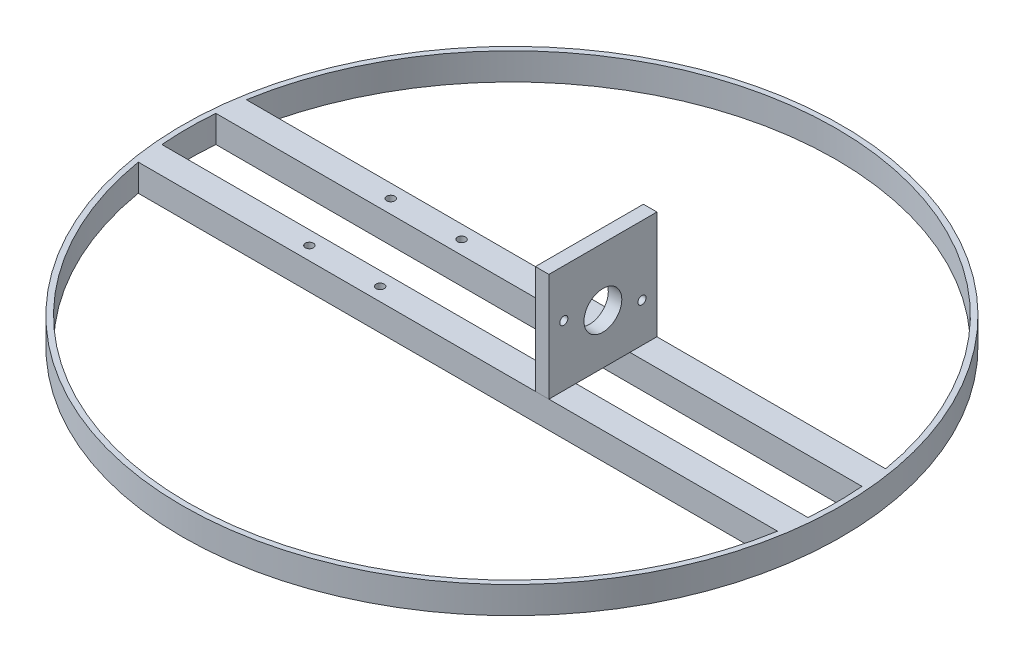
SolidWorks part; units mm, degrees
ref_plane "Front Plane" through (0, 0, 0) normal (0, 0, 1) x (1, 0, 0)
ref_plane "Top Plane" through (0, 0, 0) normal (0, 1, 0) x (1, 0, 0)
ref_plane "Right Plane" through (0, 0, 0) normal (1, 0, 0) x (0, 0, -1)
sketch "Sketch1" plane through (0, 0, 0) normal (0, 1, 0) x (1, 0, 0)
  circle A0 centre (-133.6717, -100.8607) radius 122
  circle A1 centre (-133.6717, -100.8607) radius 120
  dimension "D1" = 244
  dimension "D2" = 2
extrude "Boss-Extrude1" add sketch "Sketch1" along normal blind 10
sketch "Sketch2" plane through (0, 0, 0) normal (1, 0, 0) x (0, 0, -1)
  line L0 (-100.8607, 10) -> (-100.8607, -30.5393) construction
  line L1 (21.1393, 10) -> (-222.8607, 10) construction
  line L2 (-222.8607, 0) -> (21.1393, 0) construction
  line L3 (-120.8607, 10) -> (-110.8607, 10)
  line L4 (-120.8607, 10) -> (-120.8607, 0)
  line L5 (-120.8607, 0) -> (-110.8607, 0)
  line L6 (-110.8607, 10) -> (-110.8607, 0)
  line L8 (-90.8607, 10) -> (-90.8607, 0)
  line L9 (-80.8607, 0) -> (-90.8607, 0)
  line L10 (-80.8607, 10) -> (-80.8607, 0)
  line L11 (-80.8607, 10) -> (-90.8607, 10)
  dimension "D1" = 10
extrude "Boss-Extrude2" add sketch "Sketch2" against normal blind 300
sketch "Sketch3" plane through (0, 0, 0) normal (0, 1, 0) x (1, 0, 0)
  line L0 (-133.6717, -90.8607) -> (-133.6717, -110.8607) construction
  line L1 (-253.2543, -90.8607) -> (-14.0891, -90.8607) construction
  line L2 (-253.2543, -110.8607) -> (-14.0891, -110.8607) construction
  circle A0 centre (-133.6717, -100.8607) radius 122
extrude "Cut-Extrude5" cut sketch "Sketch3" against normal through all and the other way through all flip side to cut contours A0
sketch "Sketch4" plane through (0, 0, 0) normal (1, 0, 0) x (0, 0, -1)
  line L0 (21.1393, 10) -> (-222.8607, 10) construction
  line L1 (-120.8607, 10) -> (-80.8607, 10)
  line L2 (-120.8607, 10) -> (-120.8607, 50)
  line L3 (-120.8607, 50) -> (-80.8607, 50)
  line L4 (-80.8607, 50) -> (-80.8607, 10)
  line L5 (-120.8607, 10) -> (-220.8607, 10) construction
  line L7 (-100.8607, 50) -> (-100.8607, 10) construction
  line L8 (-100.8607, 30) -> (-80.8607, 30) construction
  circle A0 centre (-86.3892, 24.5198) radius 1.5
  circle A1 centre (-115.3323, 32.4125) radius 1.5
  circle A2 centre (-100.8607, 28.4662) radius 7
  dimension "D3" = 14
  dimension "D1" = 40
  dimension "D2" = 40
extrude "Boss-Extrude3" add sketch "Sketch4" along normal blind 5 from offset 105 separate body offset against normal yes
sketch "Sketch6" plane through (0, 0, 0) normal (0, 1, 0) x (1, 0, 0)
  line L0 (-133.6717, -80.8607) -> (-133.6717, -120.8607) construction
  line L1 (-251.9933, -80.8607) -> (-15.3501, -80.8607) construction
  line L2 (-251.9933, -120.8607) -> (-15.3501, -120.8607) construction
  circle A0 centre (-133.6717, -100.8607) radius 10
  circle A1 centre (-133.6717, -100.8607) radius 20
sketch "Sketch7" plane through (0, 10, 0) normal (0, 1, 0) x (1, 0, 0)
  circle A0 centre (-193.5824, -85.7986) radius 1.5
  circle A1 centre (-167.3811, -85.7986) radius 1.5
  circle A2 centre (-193.5824, -115.9228) radius 1.5
  circle A3 centre (-167.3811, -115.9228) radius 1.5
extrude "Cut-Extrude6" cut sketch "Sketch7" against normal blind 10
